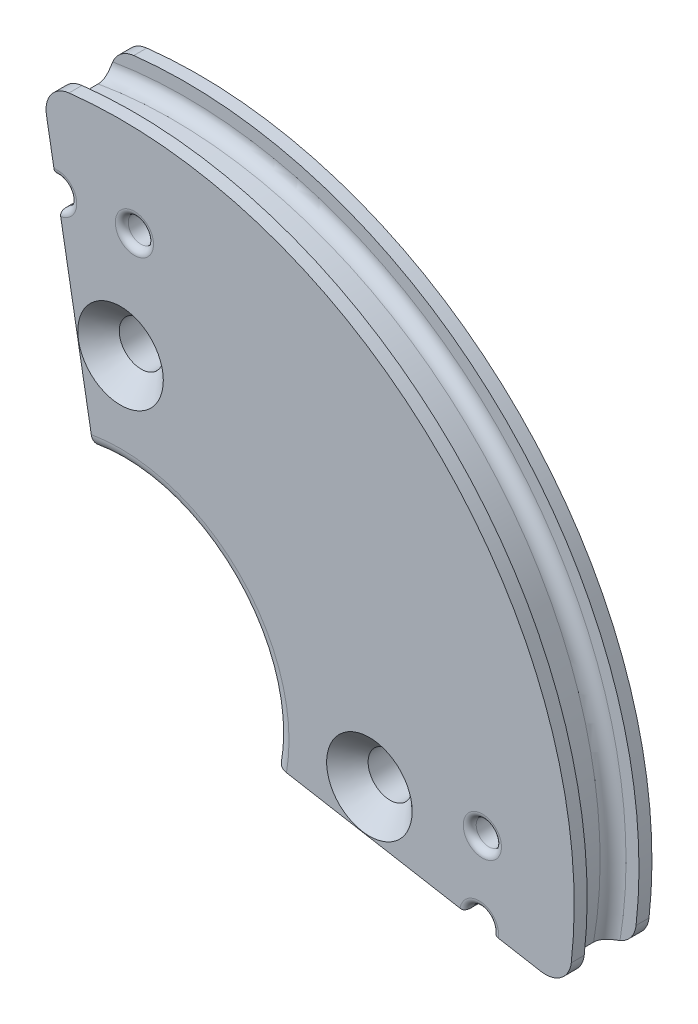
SolidWorks part; units mm, degrees
ref_plane "Front" through (0, 0, 0) normal (0, 0, 1) x (1, 0, 0)
ref_plane "Top" through (0, 0, 0) normal (0, 1, 0) x (1, 0, 0)
ref_plane "Right" through (0, 0, 0) normal (1, 0, 0) x (0, 0, -1)
sketch "Sketch1" plane through (0, 0, 0) normal (0, 0, 1) x (1, 0, 0)
  circle A2 centre (9.6, 0) radius 0.85
  circle A24 centre (0, 0) radius 17
  circle A25 centre (0, 0) radius 6
  circle A30 centre (0, -9.6) radius 0.85
  circle A32 centre (-9.6, 0) radius 0.85
  circle A34 centre (0, 9.6) radius 0.85
  point P20 (0, 0)
  dimension "D1" = 4
  dimension "D2" = 34
  dimension "D3" = 12
  dimension "D4" = 19.2
  dimension "D5" = 1.7
extrude "Boss-Extrude1" add sketch "Sketch1" along normal mid plane 3
sketch "Sketch2" plane through (0, 0, 0) normal (0, 1, 0) x (1, 0, 0)
  line L1 (0, 0) -> (0, 3.24) construction
  line L2 (17, 0) -> (19.1765, -2.75) construction
  line L3 (17, -1.5) -> (17, 1.5) construction
  line L4 (-17, 0) -> (-16.5, 0) construction
  line L5 (-17, 1.5) -> (-17, -1.5) construction
  line L6 (-16.5, -0.5) -> (-16.5, 0.5)
  line L7 (-17, 1) -> (-17, -1)
  arc A1 (-16.5, 0.5) -> (-17, 1) centre (-17, 0.5) ccw
  arc A2 (-16.5, -0.5) -> (-17, -1) centre (-17, -0.5) cw
  dimension "D1" = 33
  dimension "D2" = 2
revolve "Cut-Revolve1" cut sketch "Sketch2" angle 360 about L1
sketch "Sketch3" plane through (0, 0, 1.5) normal (0, 0, 1) x (1, 0, 0)
  line L0 (-17, 0) -> (0, 0)
  line L3 (0, 0) -> (2.952, 16.7417)
  arc A1 (-17, 0) -> (2.952, 16.7417) centre (0, 0) cw
  circle A2 centre (0, 0) radius 6 construction
  circle A3 centre (0, 0) radius 17 construction
  dimension "D4" = 100
sketch "Sketch7" plane through (0, 0, 0) normal (0, 1, 0) x (1, 0, 0)
  line L0 (1.4542, 0) -> (0, 0) construction
  line L1 (17, 1.5) -> (17.5, 1.5)
  line L2 (17, 1.5) -> (17, 1)
  line L3 (17, 1) -> (17.5, 1)
  line L4 (17.5, 1.5) -> (17.5, 1)
  line L5 (0, 0) -> (0, 3.1931) construction
  line L6 (17.5, -1.5) -> (17.5, -1)
  line L7 (17, -1) -> (17.5, -1)
  line L8 (17, -1.5) -> (17, -1)
  line L9 (17, -1.5) -> (17.5, -1.5)
  dimension "D1" = 0.5
revolve "Revolve1" add sketch "Sketch7" angle 360 about L5
sketch "Sketch4" plane through (0, 0, 0) normal (0, 0, 1) x (1, 0, 0)
  line L0 (-3.309, 18.7662) -> (0, 0)
  line L1 (0, 0) -> (12.0208, 12.0208) construction
  line L2 (0, 0) -> (-16.6927, 0) construction
  line L3 (18.7662, -3.309) -> (0, 0)
  line L5 (-3.309, 18.7662) -> (-24.9321, 18.7662)
  line L6 (-24.9321, 18.7662) -> (-24.9321, -21.7847)
  line L7 (-24.9321, -21.7847) -> (18.7662, -21.7847)
  line L10 (18.7662, -3.309) -> (18.7662, -21.7847)
  line L11 (-3.309, 18.7662) -> (18.7662, -3.309) construction
  point P0 (7.7286, 7.7286)
  dimension "D1" = 135
  dimension "D2" = 110
extrude "Cut-Extrude1" cut sketch "Sketch4" against normal through all both and the other way through all
sketch "Sketch5" plane through (0, 0, 1.5) normal (0, 0, 1) x (1, 0, 0)
  line L0 (0, 0) -> (12.3744, 12.3744) construction
  circle A0 centre (-2.4395, 13.835) radius 0.5
  circle A1 centre (0.5347, 13.9573) radius 0.4873
  arc A2 (17.2341, -3.0388) -> (-3.0388, 17.2341) centre (0, 0) ccw construction
  circle A3 centre (13.9573, 0.5347) radius 0.4873
  circle A4 centre (13.835, -2.4395) radius 0.5
  dimension "D1" = 1
extrude "Cut-Extrude2" cut sketch "Sketch5" against normal through all both and the other way through all
fillet "Fillet1" radius 0.5 2 edges at (4.2426, 4.2426, 1.5) (4.2426, 4.2426, -1.5)
chamfer "Chamfer1" distance 0.8 angle 45 2 edges at (10.45, 0, 1.5) (0.85, 9.6, 1.5)
sketch "Sketch6" plane through (0, 0, -1.5) normal (0, 0, -1) x (-1, 0, 0)
  line L0 (0, 0) -> (-12.3744, 12.3744) construction
  line L1 (-12.3744, 12.3744) -> (1.3226, 15.1171)
  line L2 (1.3226, 15.1171) -> (0, 0)
  line L3 (-12.3744, 12.3744) -> (-15.1171, -1.3226)
  line L4 (-15.1171, -1.3226) -> (0, 0)
  arc A1 (3.0388, 17.2341) -> (-17.2341, -3.0388) centre (0, 0) ccw construction
  dimension "D1" = 50
fillet "Fillet2" radius 1 2 edges at (17.2341, -3.0388, 1.25) (-3.0388, 17.2341, -1.25)
fillet "Fillet3" radius 0.25 12 edges at (-2.5263, 14.3274, 0) (-1.9471, 13.9218, 1.5) (-2.3527, 13.3426, 0) (-1.9471, 13.9218, -1.5) (13.3426, -2.3527, 0) (13.9218, -1.9471, 1.5) (14.3274, -2.5263, 0) (13.9218, -1.9471, -1.5) (13.47, 0.5347, -1.5) (14.4445, 0.5347, 1.5) (1.022, 13.9573, -1.5) (1.022, 13.9573, 1.5)
sketch "Sketch8" plane through (0, 0, 1.5) normal (0, 0, 1) x (1, 0, 0)
  circle A0 centre (0, 0) radius 17.5
